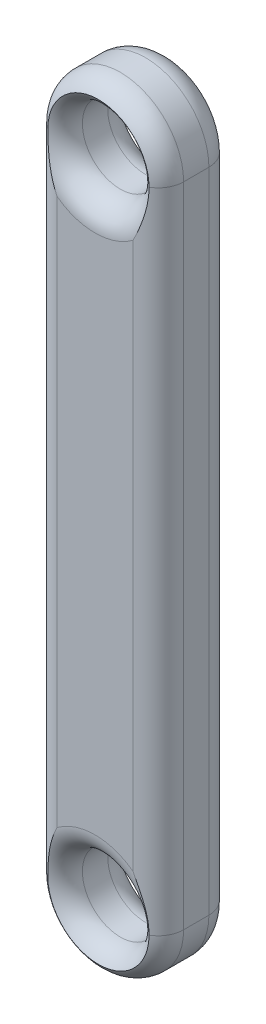
SolidWorks part; units mm, degrees
ref_plane "Front Plane" through (0, 0, 0) normal (0, 0, 1) x (1, 0, 0)
ref_plane "Top Plane" through (0, 0, 0) normal (0, 1, 0) x (1, 0, 0)
ref_plane "Right Plane" through (0, 0, 0) normal (1, 0, 0) x (0, 0, -1)
sketch "Sketch1" plane through (0, 0, 0) normal (0, 0, 1) x (1, 0, 0)
  line L0 (0, 0) -> (0, 25.6) construction
  line L1 (-2.5, 0) -> (-2.5, 25.6)
  line L2 (2.5, 0) -> (2.5, 25.6)
  arc A0 (-2.5, 0) -> (2.5, 0) centre (0, 0) ccw
  arc A1 (2.5, 25.6) -> (-2.5, 25.6) centre (0, 25.6) ccw
  circle A2 centre (0, 25.6) radius 1.5
  circle A3 centre (0, 0) radius 1.5
  point P3 (0, 12.8)
  dimension "D3" = 3
  dimension "D4" = 3
  dimension "D1" = 25.6
  dimension "D2" = 5
extrude "Boss-Extrude1" add sketch "Sketch1" along normal blind 3
fillet "Fillet2" radius 1 12 edges at (0, -2.5, 3) (0, -2.5, 0) (2.5, 12.8, 3) (2.5, 12.8, 0) (0, 28.1, 3) (0, 28.1, 0) (-2.5, 12.8, 3) (-2.5, 12.8, 0) (1.5, 25.6, 0) (1.5, 25.6, 3) (1.5, 0, 0) (1.5, 0, 3)
